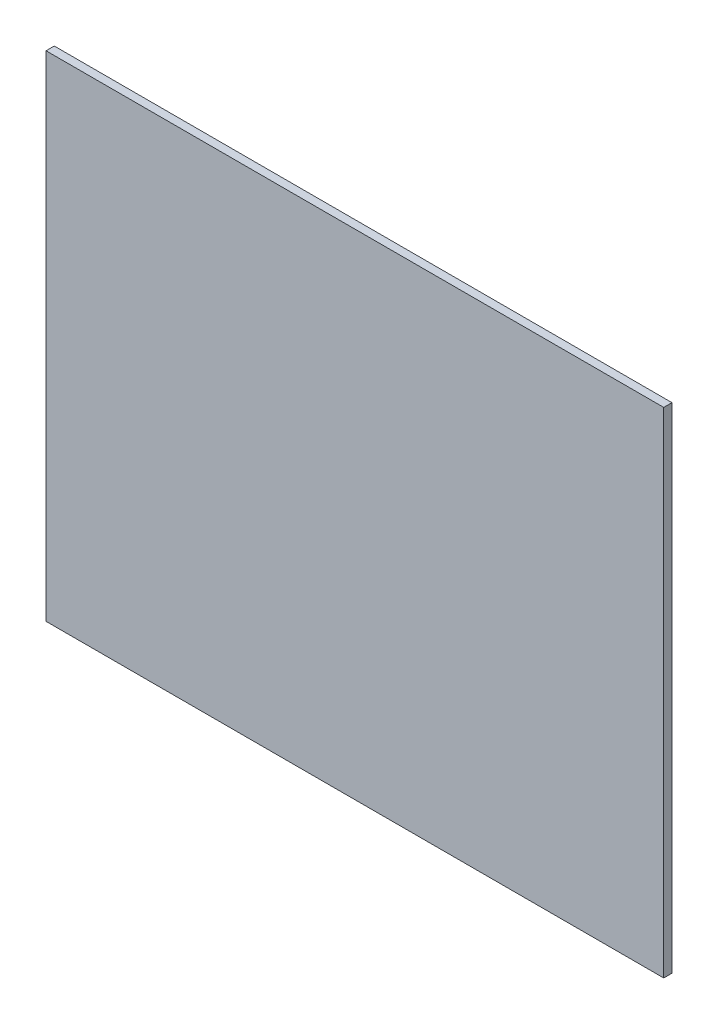
SolidWorks part; units mm, degrees
material "PC High Viscosity"
ref_plane "Front Plane" through (0, 0, 0) normal (0, 0, 1) x (1, 0, 0)
ref_plane "Top Plane" through (0, 0, 0) normal (0, 1, 0) x (1, 0, 0)
ref_plane "Right Plane" through (0, 0, 0) normal (1, 0, 0) x (0, 0, -1)
sketch "Sketch1" plane through (0, 0, 0) normal (0, 0, 1) x (1, 0, 0)
  line L1 (0, 0) -> (381, 0)
  line L2 (0, 0) -> (0, 304.8)
  line L3 (0, 304.8) -> (381, 304.8)
  line L4 (381, 0) -> (381, 304.8)
  dimension "D1" = 381
  dimension "D2" = 304.8
extrude "Boss-Extrude1" add sketch "Sketch1" along normal blind 5.08
sketch "Sketch2" plane through (0, 0, 0) normal (0, 0, -1) x (-1, 0, 0)
  line L1 (-381, 304.8) -> (0, 304.8) construction
  line L2 (-523.4473, 152.4) -> (65.789, 152.4) construction
  dimension "D4" = 152.4
sketch "Sketch3" plane through (0, 0, 0) normal (0, 0, -1) x (-1, 0, 0)
  line L0 (-247.65, 343.5749) -> (-247.65, -43.3065)
  line L1 (-381, 0) -> (-381, 304.8) construction
  circle A0 centre (-617.3035, 295.0156) radius 12.7
  circle A1 centre (-532.4341, 295.0156) radius 12.7
  circle A2 centre (-617.3035, 235.0821) radius 12.7
  circle A4 centre (-532.4341, 235.0821) radius 12.7
  circle A5 centre (-573.4436, 183.0995) radius 12.7
  circle A6 centre (-476.7814, 183.0995) radius 12.7
  circle A7 centre (-677.2371, 183.0995) radius 12.7
  circle A8 centre (-573.4436, 129.214) radius 12.7
  circle A9 centre (-476.7814, 129.214) radius 12.7
  circle A10 centre (-677.2371, 129.214) radius 12.7
  circle A11 centre (-573.4436, 76.1041) radius 12.7
  circle A12 centre (-476.7814, 76.1041) radius 12.7
  circle A13 centre (-677.2371, 76.1041) radius 12.7
  point P18 (0, 0)
  point P19 (0, 0)
  point P20 (0, 0)
  point P21 (0, 0)
  point P22 (0, 0)
  point P29 (0, 0)
  point P30 (-677.2371, 129.214)
  point P31 (0, 0)
  point P32 (0, 0)
  point P33 (0, 0)
  point P40 (-773.3559, 76.1041)
  point P41 (0, 0)
  point P42 (0, 0)
  point P43 (-573.4436, 183.0995)
  dimension "D2" = 25.4
  dimension "D3" = 25.4
  dimension "D4" = 25.4
  dimension "D5" = 25.4
  dimension "D6" = 25.4
  dimension "D7" = 25.4
  dimension "D8" = 25.4
  dimension "D9" = 25.4
  dimension "D10" = 25.4
  dimension "D11" = 25.4
  dimension "D1" = 133.35
